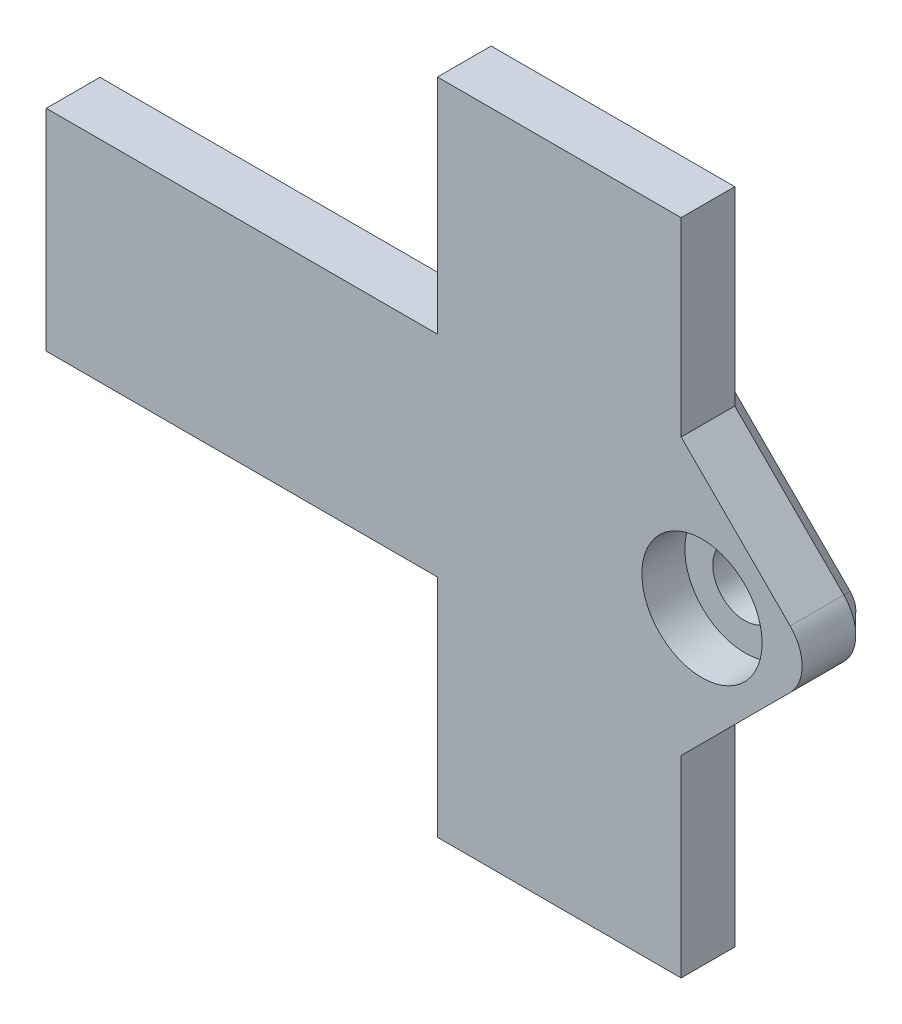
SolidWorks part; units mm, degrees
ref_plane "Front" through (0, 0, 0) normal (0, 0, 1) x (1, 0, 0)
ref_plane "Top" through (0, 0, 0) normal (0, 1, 0) x (1, 0, 0)
ref_plane "Right" through (0, 0, 0) normal (1, 0, 0) x (0, 0, -1)
sketch "Sketch1" plane through (0, 0, 0) normal (0, 0, 1) x (1, 0, 0)
  line L22 (-23.9, 4.9) -> (-23.9, -4.9)
  line L23 (-23.9, -4.9) -> (-5.675, -4.9)
  line L24 (-5.675, -4.9) -> (-5.675, -15.4)
  line L25 (-5.675, -15.4) -> (5.675, -15.4)
  line L26 (5.675, -15.4) -> (5.675, -6.4249)
  line L27 (5.675, -6.4249) -> (10.7564, -1.3435)
  line L28 (10.7564, 1.3435) -> (5.675, 6.4249)
  line L29 (5.675, 6.4249) -> (5.675, 15.275)
  line L30 (5.675, 15.275) -> (-5.675, 15.275)
  line L31 (-5.675, 15.275) -> (-5.675, 4.9)
  line L32 (-5.675, 4.9) -> (-23.9, 4.9)
  line L33 (-23.9, 4.9) -> (-23.9, -4.9)
  line L34 (-23.9, -4.9) -> (-5.675, -4.9)
  line L35 (-5.675, -4.9) -> (-5.675, -15.4)
  line L36 (-5.675, -15.4) -> (5.675, -15.4)
  line L37 (5.675, -15.4) -> (5.675, -6.4249)
  line L38 (5.675, -6.4249) -> (10.7564, -1.3435)
  line L39 (10.7564, 1.3435) -> (5.675, 6.4249)
  line L40 (5.675, 6.4249) -> (5.675, 15.275)
  line L41 (5.675, 15.275) -> (-5.675, 15.275)
  line L42 (-5.675, 15.275) -> (-5.675, 4.9)
  line L43 (-5.675, 4.9) -> (-23.9, 4.9)
  arc A2 (10.7564, -1.3435) -> (10.7564, 1.3435) centre (9.4129, 0) ccw
  arc A3 (10.7564, -1.3435) -> (10.7564, 1.3435) centre (9.4129, 0) ccw
  dimension "D1" = 0.1
extrude "Boss-Extrude1" add sketch "Sketch1" against normal up to surface (3.5 mm away)
sketch "Sketch2" plane through (0, -4.9, 0) normal (0, -1, 0) x (1, 0, 0)
  line L8 (-19.3875, -2.5) -> (-10.3875, -2.5)
  line L9 (-19.3875, -0.9) -> (-19.3875, -2.5)
  line L10 (-10.3875, -0.9) -> (-19.3875, -0.9)
  line L11 (-10.3875, -2.5) -> (-10.3875, -0.9)
  line L12 (-19.3875, -2.5) -> (-10.3875, -2.5)
  line L13 (-19.3875, -0.9) -> (-19.3875, -2.5)
  line L14 (-10.3875, -0.9) -> (-19.3875, -0.9)
  line L15 (-10.3875, -2.5) -> (-10.3875, -0.9)
  dimension "D1" = 0
extrude "Boss-Extrude2" add sketch "Sketch2" along normal blind 1 draft 45
sketch "Sketch3" plane through (0, 0, 0) normal (0, 0, 1) x (1, 0, 0)
  circle A0 centre (6.6472, 0) radius 2.8
  circle A1 centre (6.6472, 0) radius 1.5 construction
  dimension "D1" = 5.6
extrude "Cut-Extrude1" cut sketch "Sketch3" against normal blind 2
chamfer "Chamfer1" distance 1 angle 45 12 edges at (-23.9, 0, -3.5) (-14.7875, -4.9, -3.5) (-5.675, -10.15, -3.5) (0, -15.4, -3.5) (5.675, -10.9125, -3.5) (8.2157, -3.8842, -3.5) (11.3129, 0, -3.5) (8.2157, 3.8842, -3.5) (5.675, 10.85, -3.5) (0, 15.275, -3.5) (-5.675, 10.0875, -3.5) (-14.7875, 4.9, -3.5)
sketch "Sketch4" plane through (0, 0, 0) normal (0, 0, 1) x (1, 0, 0)
  circle A0 centre (6.6472, 0) radius 1.5
  dimension "D1" = 3
extrude "Cut-Extrude2" cut sketch "Sketch4" against normal through all
